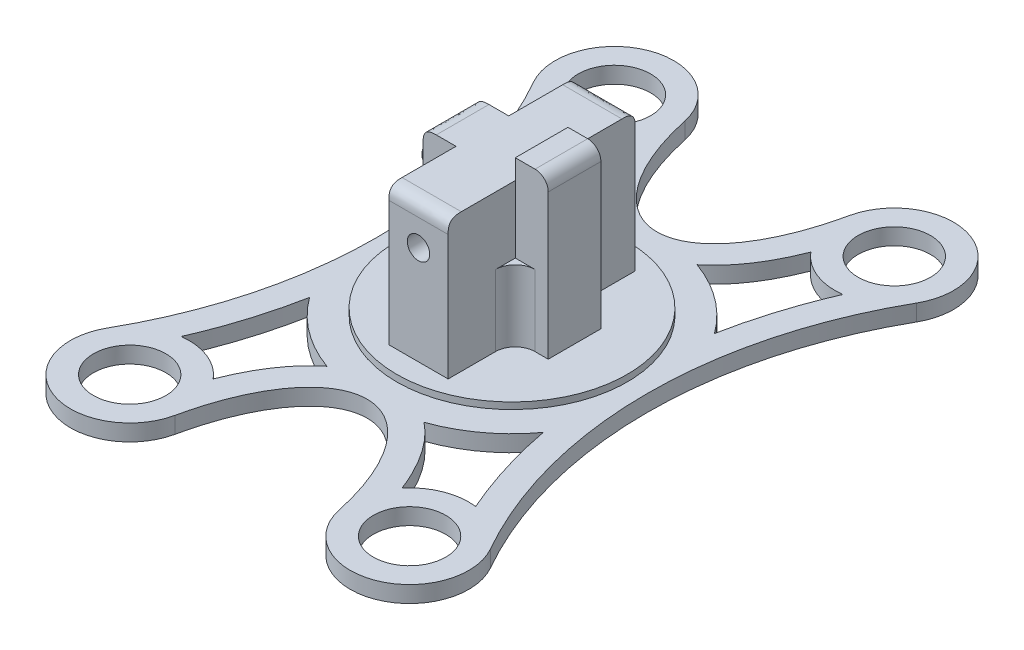
SolidWorks part; units mm, degrees
material "ABS"
ref_plane "Front Plane" through (0, 0, 0) normal (0, 0, 1) x (1, 0, 0)
ref_plane "Top Plane" through (0, 0, 0) normal (0, 1, 0) x (1, 0, 0)
ref_plane "Right Plane" through (0, 0, 0) normal (1, 0, 0) x (0, 0, -1)
sketch "Sketch1" plane through (0, 0, 0) normal (0, 1, 0) x (1, 0, 0)
  line L1 (-50, -50) -> (50, -50)
  line L2 (-50, -50) -> (-50, 50)
  line L3 (-50, 50) -> (50, 50)
  line L4 (50, -50) -> (50, 50)
  line L5 (-50, -50) -> (50, 50) construction
  line L6 (-50, 50) -> (50, -50) construction
  point P0 (0, 0)
  dimension "D1" = 100
  dimension "D2" = 100
extrude "Boss-Extrude1" add sketch "Sketch1" along normal blind 2.5
sketch "Sketch2" plane through (0, 2.5, 0) normal (0, 1, 0) x (1, 0, 0)
  line L0 (-50, -50) -> (50, -50) construction
  line L1 (50, 50) -> (-50, 50) construction
  line L2 (-21.25, 36.8061) -> (21.25, -36.8061)
  line L3 (21.25, 36.8061) -> (-21.25, -36.8061)
  line L14 (0, -15.9125) -> (0, 15.9125)
  arc A0 (-29.0749, 32.3597) -> (-12.4502, 38.6938) centre (-21.25, 36.8061) cw
  circle A1 centre (21.25, 36.8061) radius 5.5
  circle A2 centre (-21.25, 36.8061) radius 5.5
  circle A3 centre (21.25, -36.8061) radius 5.5
  circle A4 centre (-21.25, -36.8061) radius 5.5
  arc A5 (12.4502, 38.6938) -> (29.0749, 32.3597) centre (21.25, 36.8061) cw
  arc A6 (-12.4502, -38.6938) -> (-29.0749, -32.3597) centre (-21.25, -36.8061) cw
  arc A7 (12.4502, -38.6938) -> (29.0749, -32.3597) centre (21.25, -36.8061) ccw
  arc A8 (29.0749, 32.3597) -> (29.0749, -32.3597) centre (86.0232, 0) ccw
  arc A9 (-29.0749, 32.3597) -> (-29.0749, -32.3597) centre (-86.0232, 0) cw
  ellipse E0 centre (0, 50) end of major axis (0, 22) minor radius 13.609 (-12.4502, 38.6938) -> (12.4502, 38.6938) ccw
  ellipse E1 centre (0, -50) end of major axis (0, -22) minor radius 13.609 (12.4502, -38.6938) -> (-12.4502, -38.6938) ccw
  point P11 (0, 0)
  point P12 (0, 0)
  point P21 (0, 0)
  point P22 (0, 0)
  point P23 (0, -19.7376)
  point P33 (0, 0)
  point P41 (0, 0)
  dimension "D4" = 11
  dimension "D1" = 9
  dimension "D2" = 65.5
  dimension "D7" = 65.5
  dimension "D3" = 85
  dimension "D5" = 31.8249
  dimension "D6" = 60
  dimension "D8" = 28
  dimension "D9" = 28
extrude "Cut-Extrude1" cut sketch "Sketch2" against normal blind 10
sketch "Sketch4" plane through (0, 2.5, 0) normal (0, 1, 0) x (1, 0, 0)
  arc A0 (-29.0749, -32.3597) -> (-12.4502, -38.6938) centre (-21.25, -36.8061) ccw construction
  arc A1 (-17.7495, -12.9983) -> (-7.3676, -20.7296) centre (0, 0) ccw
  arc A2 (7.3676, -20.7296) -> (17.7495, -12.9983) centre (0, 0) ccw
  arc A3 (-22.3579, -27.8745) -> (-14.3451, -31.0336) centre (-21.25, -36.8061) cw
  arc A4 (22.3579, -27.8745) -> (14.3451, -31.0336) centre (21.25, -36.8061) ccw
  arc A5 (14.3451, 31.0336) -> (22.3579, 27.8745) centre (21.25, 36.8061) ccw
  arc A6 (-14.3451, 31.0336) -> (-22.3579, 27.8745) centre (-21.25, 36.8061) cw
  arc A7 (17.7495, 12.9983) -> (7.3676, 20.7296) centre (0, 0) ccw
  arc A8 (-7.3676, 20.7296) -> (-17.7495, 12.9983) centre (0, 0) ccw
  spline S0 degree 3 poles (7.3676, 20.7296) (7.7472, 21.0301) (8.1145, 21.3503) (9.2471, 22.428) (9.9675, 23.253) (11.9755, 25.9455) (13.1132, 28.0315) (14.1613, 30.5689) (14.2541, 30.8002) (14.3451, 31.0336) knots 0.658937 0.658937 0.658937 0.658937 0.6875 0.6875 0.75 0.75 0.875 0.875 0.887406 0.887406 0.887406 0.887406
  spline S1 degree 3 poles (-17.7495, -12.9983) (-18.73, -18.1485) (-20.279, -23.1263) (-22.3579, -27.8745) knots 0.6785 0.6785 0.6785 0.6785 0.896036 0.896036 0.896036 0.896036 weights 0.943039 0.949799 0.960677 0.975675
  spline S2 degree 3 poles (17.7495, 12.9983) (18.73, 18.1485) (20.279, 23.1263) (22.3579, 27.8745) knots 0.6785 0.6785 0.6785 0.6785 0.896036 0.896036 0.896036 0.896036 weights 0.943039 0.949799 0.960677 0.975675
  spline S3 degree 3 poles (-1432.768, 4724.087) (-243.33, -633.9868) (54.7255, -128.7666) (13.1132, -28.0315) (11.9755, -25.9455) (9.9675, -23.253) (9.2471, -22.428) (7.6924, -20.9487) (6.8575, -20.294) (5.0662, -19.1991) (4.1085, -18.7595) (2.1008, -18.1589) (1.0511, -18) (-1.0511, -18) (-2.1008, -18.1589) (-4.1085, -18.7595) (-5.0662, -19.1991) (-6.8575, -20.294) (-7.6924, -20.9487) (-9.2471, -22.428) (-9.9675, -23.253) (-11.9755, -25.9455) (-13.1132, -28.0315) (-54.7252, -128.766) (243.3266, -633.9809) (1432.7472, 4723.9934) knots -5.205158 -5.205158 -5.205158 -5.205158 0.125 0.125 0.25 0.25 0.3125 0.3125 0.375 0.375 0.4375 0.4375 0.5 0.5 0.5625 0.5625 0.625 0.625 0.6875 0.6875 0.75 0.75 0.875 0.875 6.205127 6.205127 6.205127 6.205127 only from (16.3612, -37.8548) to (-16.3612, -37.8548)
  spline S4 degree 3 poles (14.3451, -31.0336) (14.2541, -30.8002) (14.1613, -30.5689) (13.1132, -28.0315) (11.9755, -25.9455) (9.9675, -23.253) (9.2471, -22.428) (8.1145, -21.3503) (7.7472, -21.0301) (7.3676, -20.7296) knots 0.112594 0.112594 0.112594 0.112594 0.125 0.125 0.25 0.25 0.3125 0.3125 0.341063 0.341063 0.341063 0.341063
  spline S5 degree 3 poles (-7.3676, -20.7296) (-7.7472, -21.0301) (-8.1145, -21.3503) (-9.2471, -22.428) (-9.9675, -23.253) (-11.9755, -25.9455) (-13.1132, -28.0315) (-14.1613, -30.5689) (-14.2541, -30.8002) (-14.3451, -31.0336) knots 0.658937 0.658937 0.658937 0.658937 0.6875 0.6875 0.75 0.75 0.875 0.875 0.887406 0.887406 0.887406 0.887406
  spline S19 degree 3 poles (-25.5972, 34.3359) (-13.2101, 12.5365) (-13.2101, -12.5365) (-25.5972, -34.3359) knots 0 0 0 0 1 1 1 1 weights 1 0.912959 0.912959 1
  spline S20 degree 3 poles (-22.3579, 27.8745) (-20.279, 23.1263) (-18.73, 18.1485) (-17.7495, 12.9983) knots 0.103964 0.103964 0.103964 0.103964 0.3215 0.3215 0.3215 0.3215 weights 0.975675 0.960677 0.949799 0.943039
  spline S25 degree 3 poles (25.5972, -34.3359) (13.2101, -12.5365) (13.2101, 12.5365) (25.5972, 34.3359) knots 0 0 0 0 1 1 1 1 weights 1 0.912959 0.912959 1
  spline S26 degree 3 poles (22.3579, -27.8745) (20.279, -23.1263) (18.73, -18.1485) (17.7495, -12.9983) knots 0.103964 0.103964 0.103964 0.103964 0.3215 0.3215 0.3215 0.3215 weights 0.975675 0.960677 0.949799 0.943039
  spline S28 degree 3 poles (1432.768, -4724.087) (243.33, 633.9868) (-54.7255, 128.7666) (-13.1132, 28.0315) (-11.9755, 25.9455) (-9.9675, 23.253) (-9.2471, 22.428) (-7.6924, 20.9487) (-6.8575, 20.294) (-5.0662, 19.1991) (-4.1085, 18.7595) (-2.1008, 18.1589) (-1.0511, 18) (1.0511, 18) (2.1008, 18.1589) (4.1085, 18.7595) (5.0662, 19.1991) (6.8575, 20.294) (7.6924, 20.9487) (9.2471, 22.428) (9.9675, 23.253) (11.9755, 25.9455) (13.1132, 28.0315) (54.7252, 128.766) (-243.3266, 633.9809) (-1432.7472, -4723.9934) knots -5.205158 -5.205158 -5.205158 -5.205158 0.125 0.125 0.25 0.25 0.3125 0.3125 0.375 0.375 0.4375 0.4375 0.5 0.5 0.5625 0.5625 0.625 0.625 0.6875 0.6875 0.75 0.75 0.875 0.875 6.205127 6.205127 6.205127 6.205127 only from (-16.3612, 37.8548) to (16.3612, 37.8548)
  spline S29 degree 3 poles (-14.3451, 31.0336) (-14.2541, 30.8002) (-14.1613, 30.5689) (-13.1132, 28.0315) (-11.9755, 25.9455) (-9.9675, 23.253) (-9.2471, 22.428) (-8.1145, 21.3503) (-7.7472, 21.0301) (-7.3676, 20.7296) knots 0.112594 0.112594 0.112594 0.112594 0.125 0.125 0.25 0.25 0.3125 0.3125 0.341063 0.341063 0.341063 0.341063
  point P8 (0, 0)
  point P11 (0, 0)
  point P12 (0, 0)
  point P38 (0, 0)
  dimension "D5" = 44
  dimension "D1" = 4
  dimension "D2" = 4
  dimension "D3" = 4
  dimension "D4" = 4
extrude "Cut-Extrude3" cut sketch "Sketch4" against normal blind 10
sketch "Sketch6" plane through (0, 2.5, 0) normal (0, 1, 0) x (1, 0, 0)
  circle A0 centre (0, 0) radius 17.5
  dimension "D1" = 35
extrude "Boss-Extrude2" add sketch "Sketch6" along normal blind 1 and the other way offset from surface (4.5 mm away) 2 other way up to face at (-14.5231, 0, 21.8434)
sketch "Sketch9" plane through (0, 3.5, 0) normal (0, 1, 0) x (1, 0, 0)
  line L0 (-4.5, 4) -> (-9.5, 4)
  line L1 (-4.5, -14.2) -> (4.5, -14.2)
  line L2 (-4.5, -14.2) -> (-4.5, -4)
  line L3 (-4.5, 14.2) -> (4.5, 14.2)
  line L4 (4.5, -14.2) -> (4.5, 14.2)
  line L5 (4.5, 14.2) -> (-4.5, -14.2) construction
  line L6 (4.5, -14.2) -> (-4.5, 14.2) construction
  line L7 (-9.5, 4) -> (-9.5, -4)
  line L8 (-9.5, -4) -> (-4.5, -4)
  line L9 (-4.5, 4) -> (-4.5, 14.2)
  point P0 (0, 0)
  point P1 (0, 0)
  point P6 (-9.5, 0)
  point P7 (4.5, 0)
  point P12 (0, 0)
  point P16 (0, 0)
  dimension "D1" = 28.4
  dimension "D2" = 14
  dimension "D3" = 9
  dimension "D4" = 8
extrude "Boss-Extrude6" add sketch "Sketch9" along normal blind 21
fillet "Fillet1" radius 2 1 edges at (-9.5, 24.5, 0)
fillet "Fillet2" radius 2 2 edges at (0, 24.5, 14.2) (0, 24.5, -14.2)
sketch "Sketch12" plane through (0, 0, -14.2) normal (0, 0, -1) x (-1, 0, 0)
  line L1 (-4.5, 22.5) -> (-4.5, 3.5) construction
  line L2 (-4.5, 24.5) -> (4.5, 24.5) construction
  circle A0 centre (0, 18.5) radius 1.7
  dimension "D3" = 3.4
  dimension "D1" = 6
  dimension "D2" = 4.5
extrude "Cut-Extrude4" cut sketch "Sketch12" against normal through all
sketch "Sketch13" plane through (-9.5, 0, 0) normal (-1, 0, 0) x (0, 0, 1)
  line L1 (-4, 22.5) -> (-4, 3.5) construction
  line L2 (-4, 24.5) -> (4, 24.5) construction
  circle A0 centre (0, 18.5) radius 1.7
  dimension "D1" = 3.4
  dimension "D2" = 6
  dimension "D3" = 4
extrude "Boss-Extrude8" add sketch "Sketch13" along normal blind 2.5
sketch "Sketch16" plane through (0, 3.5, 0) normal (0, 1, 0) x (1, 0, 0)
  line L1 (9.5, 4) -> (4.5, 4)
  line L2 (9.5, 4) -> (9.5, -4)
  line L3 (9.5, -4) -> (4.5, -4)
  line L4 (4.5, 4) -> (4.5, -4)
  dimension "D1" = 5
  dimension "D2" = 8
extrude "Boss-Extrude9" add sketch "Sketch16" along normal offset from surface (24 mm away) 3 up to face at (-3, 24.5, 0) offset beyond the face yes
fillet "Fillet3" radius 2 1 edges at (9.5, 27.5, 0)
sketch "Sketch18" plane through (0, 3.5, 0) normal (0, 1, 0) x (1, 0, 0)
  line L0 (-9.5, -4) -> (-7.5, -4)
  line L1 (-4.5, -4) -> (-4.5, -12.2) construction
  line L2 (-4.5, -7) -> (-4.5, -14.2)
  line L3 (-4.5, -14.2) -> (4.5, -14.2)
  line L4 (4.5, -14.2) -> (4.5, -7)
  line L5 (4.5, -14.2) -> (4.5, -4) construction
  line L6 (4.5, -4) -> (9.5, -4) construction
  line L7 (7.5, -4) -> (9.5, -4)
  line L8 (9.5, -4) -> (9.5, 4)
  line L9 (9.5, 4) -> (7.5, 4)
  line L10 (9.5, 4) -> (4.5, 4) construction
  line L11 (4.5, 4) -> (4.5, 14.2) construction
  line L12 (4.5, 7) -> (4.5, 14.2)
  line L13 (4.5, 14.2) -> (-4.5, 14.2)
  line L14 (-4.5, 14.2) -> (-4.5, 7)
  line L15 (-4.5, 12.2) -> (-4.5, 4) construction
  line L16 (-7.5, 4) -> (-9.5, 4)
  line L17 (-9.5, 4) -> (-9.5, -4)
  arc A0 (-7.5, -4) -> (-4.5, -7) centre (-7.5, -7) cw
  arc A1 (4.5, -7) -> (7.5, -4) centre (7.5, -7) cw
  arc A2 (7.5, 4) -> (4.5, 7) centre (7.5, 7) cw
  arc A3 (-4.5, 7) -> (-7.5, 4) centre (-7.5, 7) cw
extrude "Boss-Extrude10" add sketch "Sketch18" along normal blind 10.8
